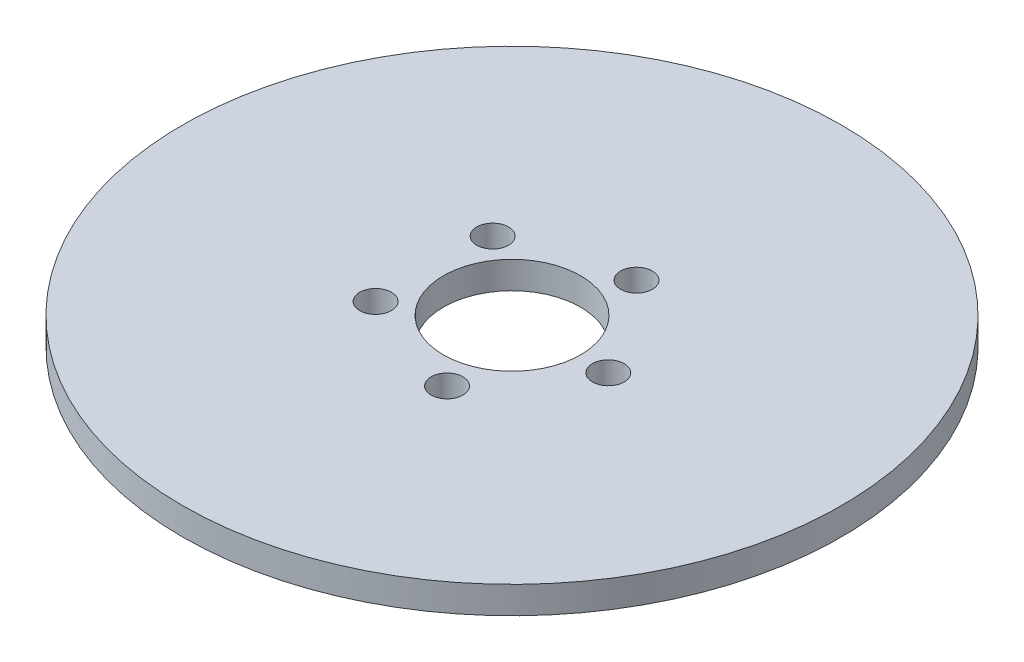
SolidWorks part; units mm, degrees
material "6061 Alloy"
ref_plane "Front Plane" through (0, 0, 0) normal (0, 0, 1) x (1, 0, 0)
ref_plane "Top Plane" through (0, 0, 0) normal (0, 1, 0) x (1, 0, 0)
ref_plane "Right Plane" through (0, 0, 0) normal (1, 0, 0) x (0, 0, -1)
sketch "Sketch1" plane through (0, 1054.464, 0) normal (0, 1, 0) x (-1, 0, 0)
  circle A0 centre (1.2041, -633.1149) radius 38.45
  circle A2 centre (1.2041, -633.1149) radius 38.45 construction
  circle A3 centre (10.3365, -639.9883) radius 1.8542 construction
  circle A4 centre (-2.5108, -643.9243) radius 1.8542 construction
  circle A5 centre (-10.2243, -632.9221) radius 1.8542 construction
  circle A6 centre (10.5632, -626.5534) radius 1.8542 construction
  circle A7 centre (-2.1441, -622.1863) radius 1.8542 construction
  circle A8 centre (1.2041, -633.1149) radius 8.001
  circle A9 centre (10.3365, -639.9883) radius 1.8542
  circle A10 centre (-2.5108, -643.9243) radius 1.8542
  circle A11 centre (-10.2243, -632.9221) radius 1.8542
  circle A12 centre (10.5632, -626.5534) radius 1.8542
  circle A13 centre (-2.1441, -622.1863) radius 1.8542
  dimension "D1" = 16.002
extrude "Boss-Extrude1" add sketch "Sketch1" against normal blind 3.175
